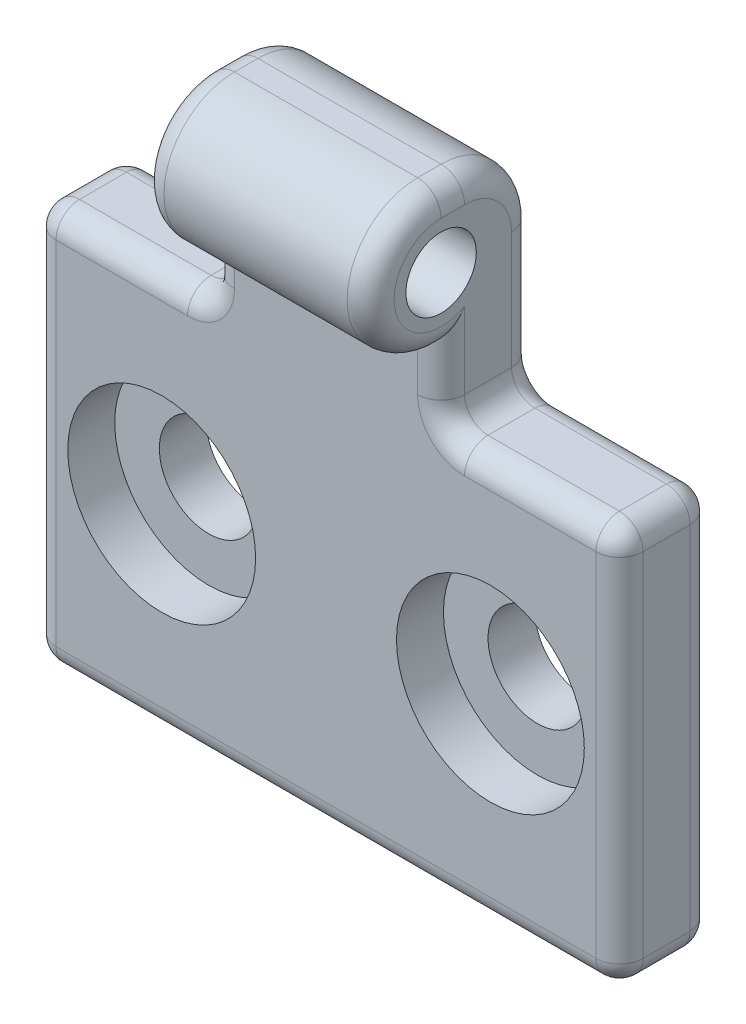
SolidWorks part; units mm, degrees
ref_plane "Plan de face" through (0, 0, 0) normal (0, 0, 1) x (1, 0, 0)
ref_plane "Plan de dessus" through (0, 0, 0) normal (0, 1, 0) x (1, 0, 0)
ref_plane "Plan de droite" through (0, 0, 0) normal (1, 0, 0) x (0, 0, -1)
sketch "Esquisse1" plane through (0, 0, 0) normal (0, 0, 1) x (1, 0, 0)
  line L1 (0, 0) -> (25, 0)
  line L2 (0, 0) -> (0, 26)
  line L3 (0, 26) -> (25, 26)
  line L4 (25, 0) -> (25, 26)
  dimension "D1" = 25
  dimension "D2" = 26
extrude "Boss.-Extru.1" add sketch "Esquisse1" along normal blind 4
sketch "Esquisse2" plane through (25, 0, 0) normal (1, 0, 0) x (0, 0, -1)
  line L4 (0, 0) -> (0, 26)
  line L5 (0, 26) -> (-4, 26)
  line L6 (-4, 26) -> (-4, 0)
  line L7 (-4, 0) -> (0, 0)
  line L8 (0, 0) -> (0, 26)
  line L9 (0, 26) -> (-4, 26)
  line L10 (-4, 26) -> (-4, 0)
  line L11 (-4, 0) -> (0, 0)
  circle A0 centre (-4, 23) radius 3
  line M7 (-4, 26) -> (-4, 0)
  dimension "D2" = 6
  dimension "D1" = 0
extrude "Boss.-Extru.2" add sketch "Esquisse2" against normal blind 25 contours A0 M7 region at (25, 23, 5.2732)
sketch "Esquisse3" plane through (25, 0, 0) normal (1, 0, 0) x (0, 0, -1)
  line L4 (0, 0) -> (0, 26)
  line L5 (0, 26) -> (-4, 26)
  line L6 (-4, 20) -> (-4, 0)
  line L7 (-4, 0) -> (0, 0)
  line L8 (0, 0) -> (0, 23)
  line L9 (-3, 26) -> (-4, 26)
  line L10 (-4, 20) -> (-4, 0)
  line L11 (-4, 0) -> (0, 0)
  arc A0 (0, 23) -> (-3, 26) centre (-3, 23) ccw
  arc A1 (-4, 26) -> (-4, 20) centre (-4, 23) ccw
  arc A2 (-4, 26) -> (-4, 20) centre (-4, 23) ccw
  circle A3 centre (-4, 23) radius 1.5
  line M6 (0, 0) -> (0, 26)
  line M7 (0, 26) -> (-4, 26)
  dimension "D2" = 3
  dimension "D3" = 3
  dimension "D1" = 0
extrude "Enlèv. mat.-Extru.1" cut sketch "Esquisse3" against normal blind 25 contours A3 | A0 M6 M7 region at (25, 25.3299, 0.6701) region at (25, 23, 4)
sketch "Esquisse4" plane through (0, 0, 4) normal (0, 0, 1) x (1, 0, 0)
  line L0 (25, 0) -> (25, 20) construction
  line L1 (0, 0) -> (25, 0)
  line L2 (0, 0) -> (0, 8.515)
  line L3 (0, 8.515) -> (25, 8.515)
  line L4 (25, 0) -> (25, 8.515)
  line L6 (0, 26) -> (7.6, 26)
  line L7 (0, 26) -> (0, 17)
  line L8 (0, 17) -> (7.6, 17)
  line L9 (25, 0) -> (25, 20)
  line L10 (25, 20) -> (0, 20)
  line L11 (0, 20) -> (0, 0)
  line L12 (0, 0) -> (25, 0)
  line L13 (25, 0) -> (25, 20)
  line L14 (25, 20) -> (0, 20)
  line L15 (0, 20) -> (0, 0)
  line L16 (0, 0) -> (25, 0)
  line L17 (25, 20) -> (25, 26)
  line L18 (25, 26) -> (0, 26)
  line L19 (0, 26) -> (0, 20)
  line L20 (0, 20) -> (25, 20)
  line L21 (25, 20) -> (25, 26)
  line L22 (25, 26) -> (0, 26)
  line L23 (0, 26) -> (0, 20)
  line L24 (0, 20) -> (25, 20)
  line L25 (7.6, 26) -> (7.6, 17)
  line L26 (25, 26) -> (17.4, 26)
  line L27 (25, 26) -> (25, 17)
  line L28 (25, 17) -> (17.4, 17)
  line L29 (17.4, 26) -> (17.4, 17)
  point P7 (5.5, 8.515)
  point P8 (19.5, 8.515)
  line M16 (25, 20) -> (0, 20)
  line M17 (0, 20) -> (0, 0)
  dimension "D1" = 5.5
  dimension "D2" = 5.5
  dimension "D5" = 7.6
  dimension "D6" = 7.6
  dimension "D7" = 9
  dimension "D8" = 9
  dimension "D3" = 0
  dimension "D4" = 0
extrude "Enlèv. mat.-Extru.2" cut sketch "Esquisse4" against normal blind 25 and the other way blind 25 contours L25 L24 L8 M17 | L25 L6 L7 L24 | L22 L29 L21 M16 | L29 L28 L13 M16 region at (3.8, 18.5, 4) region at (21.2, 18.5, 4) region at (3.8, 23, 4) region at (21.2, 23, 4)
hole_wizard "Chambrage pour vis à six pans creux M41" positions "Esquisse3D1" profile "Esquisse5" counterbore size "M4" standard "ISO" end condition through all
sketch3d "Esquisse3D1"
  point P0 (5.5, 8.515, 4)
  point P3 (19.5, 8.515, 4)
sketch "Esquisse5" plane through (5.5, 8.515, 4) normal (1, 0, 0) x (0, -1, 0)
  line L0 (0, 0) -> (0, 4)
  line L1 (0, 4) -> (2.1, 4)
  line L3 (2.1, 4) -> (2.1, 2)
  line L4 (2.1, 2) -> (4, 2)
  line L5 (4, 2) -> (4, 0)
  line L7 (4, 0) -> (0, 0)
  line L11 (0, -6.35) -> (0, 107.95) construction
  dimension "Diamètre du perçage jusqu'au prochain" = 4.2
  dimension "Profondeur du perçage jusqu'au prochain" = 4
  dimension "Diamètre du chambrage" = 8
  dimension "Profondeur du chambrage" = 2
fillet "Congé1" radius 1 26 edges at (7.6, 23, 7) (7.6, 26, 3.5) (7.6, 25.1213, 0.8787) (7.6, 20, 0) (7.6, 18.5, 4) (17.4, 20, 0) (17.4, 25.1213, 0.8787) (17.4, 26, 3.5) (12.5, 0, 4) (12.5, 0, 0) (0, 8.5, 4) (0, 0, 2) (0, 8.5, 0) (3.8, 17, 0) (7.6, 17, 2) (3.8, 17, 4) (0, 17, 2) (25, 0, 2) (25, 8.5, 4) (25, 8.5, 0) (25, 17, 2) (21.2, 17, 4) (17.4, 17, 2) (21.2, 17, 0) (17.4, 18.5, 4) (17.4, 23, 7)
